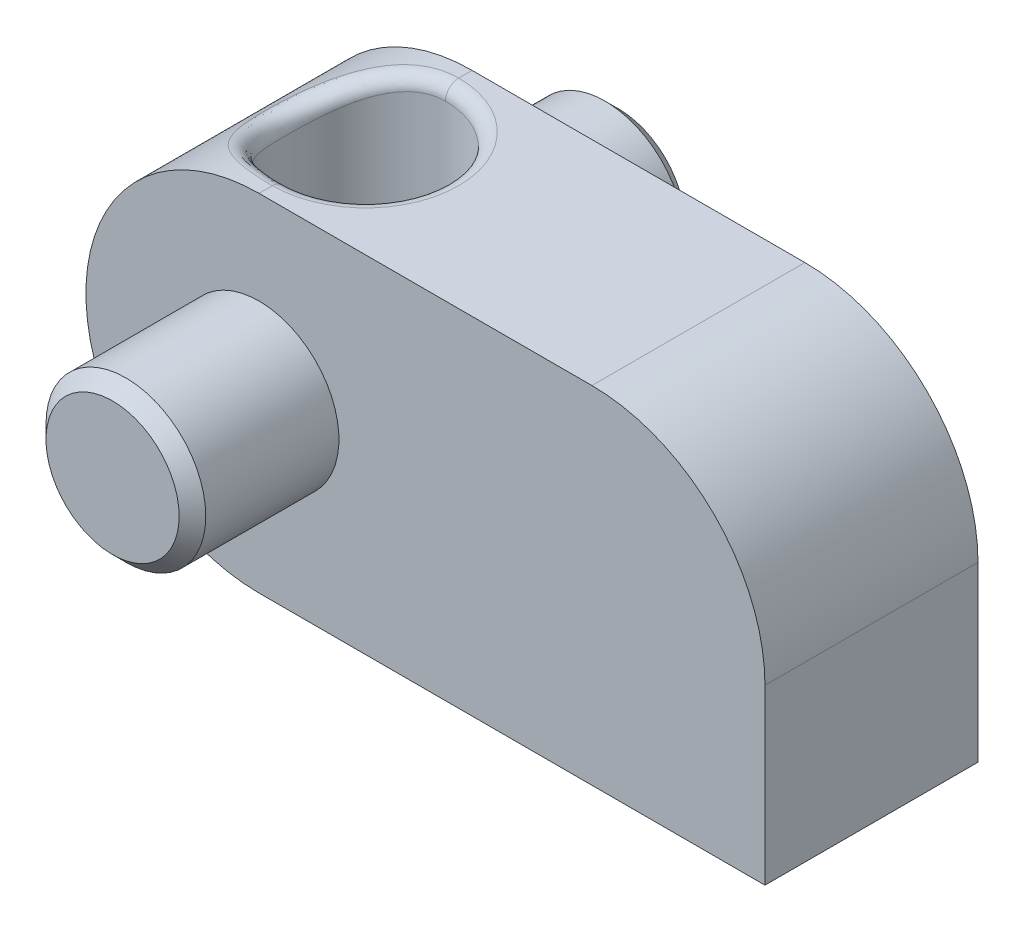
SolidWorks part; units mm, degrees
ref_plane "Plan de face" through (0, 0, 0) normal (0, 0, 1) x (1, 0, 0)
ref_plane "Plan de dessus" through (0, 0, 0) normal (0, 1, 0) x (1, 0, 0)
ref_plane "Plan de droite" through (0, 0, 0) normal (1, 0, 0) x (0, 0, -1)
sketch "Esquisse1" plane through (0, 0, 0) normal (0, 0, 1) x (1, 0, 0)
  line L0 (0, -6.5) -> (0, 6.5) construction
  line L1 (0, -6.5) -> (19, -6.5)
  line L2 (9.5, -6.5) -> (9.5, 6.5) construction
  line L3 (9.5, 6.5) -> (0, 6.5) construction
  line L5 (19, -6.5) -> (19, 6.5) construction
  line L6 (0, 6.5) -> (12.5, 6.5)
  line L7 (19, 0) -> (9.5, 0) construction
  line L8 (19, -6.5) -> (19, 0)
  arc A1 (0, -6.5) -> (0, 6.5) centre (0, 0) cw
  arc A3 (19, 0) -> (12.5, 6.5) centre (12.5, 0) ccw
  dimension "D1" = 13
extrude "Boss.-Extru.1" add sketch "Esquisse1" along normal blind 8
sketch "Esquisse3" plane through (0, -6.5, 0) normal (0, -1, 0) x (1, 0, 0)
  line L0 (19, 4) -> (0, 4) construction
  line L1 (19, 8) -> (19, 0) construction
  line L2 (0, 8) -> (0, 0) construction
  line L3 (14, 8) -> (14, 0) construction
  line L4 (0, 8) -> (19, 8) construction
  line L5 (0, 0) -> (19, 0) construction
  circle A0 centre (14, 4) radius 1.2
  dimension "D2" = 2.4
  dimension "D1" = 5
extrude "Enlèv. mat.-Extru.1" cut sketch "Esquisse3" against normal blind 12
sketch "Esquisse5" plane through (0, 0, 8) normal (0, 0, 1) x (1, 0, 0)
  circle A0 centre (0, 0) radius 3
extrude "Boss.-Extru.2" add sketch "Esquisse5" along normal blind 5.5
chamfer "Chanfrein2" distance 0.5 angle 45 1 edges at (14, -6.5, 2.8)
sketch "Esquisse7" plane through (0, 6.5, 0) normal (0, 1, 0) x (1, 0, 0)
  circle A0 centre (0, -4) radius 3
extrude "Enlèv. mat.-Extru.3" cut sketch "Esquisse7" against normal up to next
sketch "Esquisse8" plane through (0, 0, 0) normal (0, 0, -1) x (-1, 0, 0)
  circle A0 centre (0, 0) radius 3
extrude "Boss.-Extru.3" add sketch "Esquisse8" along normal blind 5.5
chamfer "Chanfrein3" distance 0.5 angle 45 2 edges at (-3, 0, -5.5) (3, 0, 13.5)
fillet "Congé1" radius 0.5 2 edges at (3, 6.5, 4) (-2.9924, 5.7702, 4.2137)
